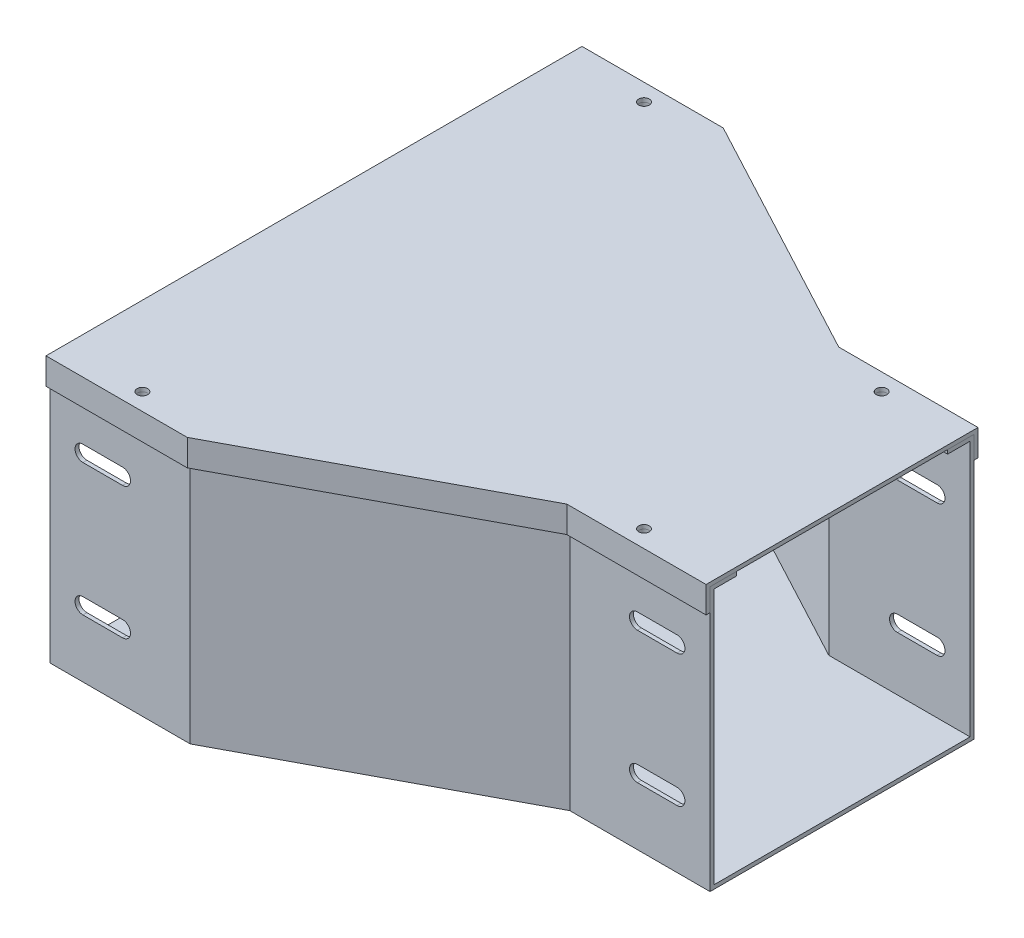
SolidWorks part; units mm, degrees
material "Plain Carbon Steel"
ref_plane "Front Plane" through (0, 0, 0) normal (0, 0, 1) x (1, 0, 0)
ref_plane "Top Plane" through (0, 0, 0) normal (0, 1, 0) x (1, 0, 0)
ref_plane "Right Plane" through (0, 0, 0) normal (1, 0, 0) x (0, 0, -1)
ref_plane "Plane1" through (0, -50, 0) normal (0, 1, 0) x (1, 0, 0)
sketch "Sketch1" plane through (0, -50, 0) normal (0, 1, 0) x (1, 0, 0)
  line L2 (100, 50) -> (100, -50)
  line L3 (-100, 100) -> (-100, -100)
  line L4 (-46.875, 100) -> (0, 75)
  line L5 (100, -50) -> (46.875, -50)
  line L6 (0, 75) -> (46.875, 50)
  line L7 (-46.875, -100) -> (0, -75)
  line L8 (-100, 100) -> (-46.875, 100)
  line L9 (-100, -100) -> (-46.875, -100)
  line L10 (0, -75) -> (46.875, -50)
  line L11 (100, 50) -> (46.875, 50)
  line L12 (0, 75) -> (0, -75) construction
  line L13 (-100, 0) -> (100, 0) construction
  dimension "Length" = 200
  dimension "Width2" = 100
  dimension "Width1" = 200
extrude "Boss-Extrude1" add sketch "Sketch1" along normal blind 1.5
sketch "Sketch2" plane through (0, -50, 0) normal (0, -1, 0) x (-1, 0, 0)
  line L0 (-46.875, 50) -> (46.875, 100) construction
  line L1 (-46.875, -50) -> (-100, -50) construction
  line L2 (100, -100) -> (46.875, -100) construction
  line L3 (-46.875, -50) -> (-100, -50)
  line L4 (100, -100) -> (46.875, -100)
  line L5 (-100, 50) -> (-46.875, 50) construction
  line L6 (46.875, 100) -> (100, 100) construction
  line L7 (-100, 50) -> (-46.875, 50)
  line L8 (46.875, 100) -> (100, 100)
  line L9 (46.875, -100) -> (-46.875, -50) construction
  line L10 (-46.875, 50) -> (46.875, 100)
  line L11 (46.875, -100) -> (-46.875, -50)
extrude "Extrude-Thin1" add sketch "Sketch2" against normal blind 100 thin thin type one direction wall 1.5
sketch "Sketch3" plane through (0, 0, 0) normal (0, 0, 1) x (1, 0, 0)
  line L0 (72.5, 25) -> (87.5, 25) construction
  line L1 (72.5, 28) -> (87.5, 28)
  line L2 (72.5, 22) -> (87.5, 22)
  line L3 (72.5, -25) -> (87.5, -25) construction
  line L4 (72.5, -22) -> (87.5, -22)
  line L5 (72.5, -28) -> (87.5, -28)
  line L6 (60, 0) -> (100, 0) construction
  line L7 (100, -48.5) -> (100, 50) construction
  line L8 (-87.5, 25) -> (-72.5, 25) construction
  line L9 (80, -50) -> (80, 0) construction
  line L10 (-87.5, 28) -> (-72.5, 28)
  line L11 (80, 0) -> (80, 50) construction
  line L12 (-87.5, 22) -> (-72.5, 22)
  line L13 (-87.5, -25) -> (-72.5, -25) construction
  line L14 (-87.5, -22) -> (-72.5, -22)
  line L15 (-87.5, -28) -> (-72.5, -28)
  line L16 (-100, 0) -> (-60, 0) construction
  line L17 (-80, -50) -> (-80, 0) construction
  line L18 (-80, 0) -> (-80, 50) construction
  line L19 (-100, -48.5) -> (-100, 50) construction
  arc A0 (72.5, 28) -> (72.5, 22) centre (72.5, 25) ccw
  arc A1 (87.5, 22) -> (87.5, 28) centre (87.5, 25) ccw
  arc A2 (72.5, -22) -> (72.5, -28) centre (72.5, -25) ccw
  arc A3 (87.5, -28) -> (87.5, -22) centre (87.5, -25) ccw
  arc A4 (-87.5, 28) -> (-87.5, 22) centre (-87.5, 25) ccw
  arc A5 (-72.5, 22) -> (-72.5, 28) centre (-72.5, 25) ccw
  arc A6 (-87.5, -22) -> (-87.5, -28) centre (-87.5, -25) ccw
  arc A7 (-72.5, -28) -> (-72.5, -22) centre (-72.5, -25) ccw
  point P2 (80, 25)
  point P8 (80, -25)
  point P22 (-80, 25)
  point P30 (-80, -25)
  dimension "D1" = 3
  dimension "D6" = 3
  dimension "D2" = 15
  dimension "D3" = 50
  dimension "D4" = 40
  dimension "D5" = 50
extrude "Cut-Extrude1" cut sketch "Sketch3" against normal through all and the other way through all
sketch "Sketch4" plane through (0, 50, 0) normal (0, 1, 0) x (1, 0, 0)
  line L0 (-100, -100) -> (-46.875, -100) construction
  line L2 (46.875, -50) -> (100, -50) construction
  line L3 (-46.875, 100) -> (-100, 100) construction
  line L5 (100, 50) -> (46.875, 50) construction
  line L6 (-100, -100) -> (-46.875, -100)
  line L7 (-46.875, -100) -> (46.875, -50)
  line L8 (46.875, -50) -> (100, -50)
  line L9 (-46.875, 100) -> (-100, 100)
  line L10 (46.875, 50) -> (-46.875, 100)
  line L11 (100, 50) -> (46.875, 50)
  line L12 (-46.875, -100) -> (46.875, -50) construction
  line L13 (46.875, 50) -> (-46.875, 100) construction
extrude "Extrude-Thin2" add sketch "Sketch4" against normal blind 1.5 thin thin type one direction reverse wall 10
sketch "Sketch5" plane through (0, 50, 0) normal (0, 1, 0) x (1, 0, 0)
  line L0 (100, 40) -> (100, 50) construction
  line L1 (100, -50) -> (100, -40) construction
  line L2 (-100, 100) -> (-100, 90) construction
  line L3 (-100, -90) -> (-100, -100) construction
  circle A0 centre (-70, 95) radius 2
  circle A1 centre (-70, -95) radius 2
  circle A2 centre (70, 45) radius 2
  circle A3 centre (70, -45) radius 2
  point P10 (100, 45)
  point P13 (100, -45)
  point P16 (-100, 95)
  point P19 (-100, -95)
  dimension "D1" = 30
  dimension "D3" = 4
  dimension "D2" = 30
extrude "Cut-Extrude2" cut sketch "Sketch5" against normal up to next
sketch "Sketch6" plane through (0, 50, 0) normal (0, 1, 0) x (1, 0, 0)
  line L8 (-46.875, -100) -> (0, -75)
  line L9 (-46.875, 100) -> (-100, 100)
  line L10 (-100, 100) -> (-100, -100)
  line L11 (-100, -100) -> (-46.875, -100)
  line L12 (-46.875, -100) -> (0, -75)
  line L13 (46.875, -50) -> (100, -50)
  line L14 (100, -50) -> (100, 50)
  line L15 (100, 50) -> (46.875, 50)
  line L16 (0, -75) -> (46.875, -50)
  line L17 (-46.875, 100) -> (-100, 100)
  line L18 (-100, 100) -> (-100, -100)
  line L19 (-100, -100) -> (-46.875, -100)
  line L20 (0, -75) -> (46.875, -50)
  line L21 (46.875, -50) -> (100, -50)
  line L22 (100, -50) -> (100, 50)
  line L23 (100, 50) -> (46.875, 50)
  line L26 (46.875, 50) -> (0, 75)
  line L27 (46.875, 50) -> (0, 75)
  line L28 (0, 75) -> (-46.875, 100)
  line L29 (0, 75) -> (-46.875, 100)
  dimension "D1" = 0
extrude "Boss-Extrude2" add sketch "Sketch6" along normal blind 1.5 separate body
sketch "Sketch7" plane through (0, 51.5, 0) normal (0, 1, 0) x (1, 0, 0)
  line L0 (100, 50) -> (46.875, 50) construction
  line L2 (-46.875, 100) -> (-100, 100) construction
  line L3 (46.875, -50) -> (100, -50) construction
  line L5 (-100, -100) -> (-46.875, -100) construction
  line L6 (100, 50) -> (46.875, 50)
  line L7 (46.875, 50) -> (-46.875, 100)
  line L8 (-46.875, 100) -> (-100, 100)
  line L9 (46.875, -50) -> (100, -50)
  line L10 (-46.875, -100) -> (46.875, -50)
  line L11 (-100, -100) -> (-46.875, -100)
  line L12 (46.875, 50) -> (-46.875, 100) construction
  line L13 (-46.875, -100) -> (46.875, -50) construction
extrude "Extrude-Thin3" add sketch "Sketch7" against normal blind 10 thin thin type one direction wall 1.5
sketch "Sketch8" plane through (0, 51.5, 0) normal (0, 1, 0) x (1, 0, 0)
  circle A1 centre (70, -45) radius 2
  circle A2 centre (70, -45) radius 2
  circle A3 centre (70, 45) radius 2
  circle A4 centre (70, 45) radius 2
  circle A5 centre (-70, -95) radius 2
  circle A6 centre (-70, -95) radius 2
  circle A7 centre (-70, 95) radius 2
  circle A8 centre (-70, 95) radius 2
  dimension "D1" = 0
  dimension "D2" = 0
  dimension "D3" = 0
  dimension "D4" = 0
extrude "Cut-Extrude3" cut sketch "Sketch8" against normal up to next (1.5 mm away)
sketch "Sketch9" plane through (0, 0, 0) normal (0, -1, 0) x (-1, 0, 0)
  line L0 (-100, -50) -> (-100, 50) construction
  line L1 (100, 100) -> (100, -100) construction
  point P0 (100, 0)
  point P1 (0, 0)
  point P2 (-100, 0)
other "CPoint1" parameters "Diameter"=10, "StubLength"=200
ref_axis "Axis2" through (-110, 0, 0) along (1, 0, 0)
other "CPoint2" parameters "Diameter"=10, "StubLength"=100
ref_axis "Axis1" through (110, 0, 0) along (-1, 0, 0)
other "RPoint1"
equation "\"D5@Extrude-Thin1\"=\"Thickness@Boss-Extrude1\""
equation "\"D3@Sketch3\"=\"Height@Extrude-Thin1\"/2"
equation "\"D5@Sketch3\"=\"Height@Extrude-Thin1\"/2"
